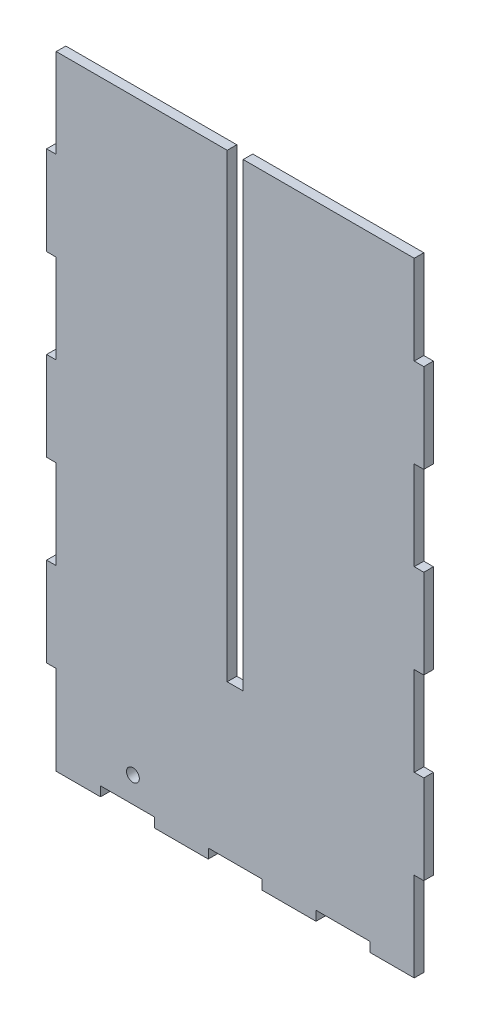
SolidWorks part; units mm, degrees
ref_plane "Front Plane" through (0, 0, 0) normal (0, 0, 1) x (1, 0, 0)
ref_plane "Top Plane" through (0, 0, 0) normal (0, 1, 0) x (1, 0, 0)
ref_plane "Right Plane" through (0, 0, 0) normal (1, 0, 0) x (0, 0, -1)
sketch "Sketch2" plane through (0, 0, 0) normal (0, 0, 1) x (1, 0, 0)
  line L0 (0, 152.4) -> (0, -152.4) construction
  line L1 (-88.9, 152.4) -> (88.9, 152.4)
  line L2 (-88.9, 152.4) -> (-88.9, -152.4)
  line L3 (-88.9, -152.4) -> (88.9, -152.4)
  line L4 (88.9, 152.4) -> (88.9, -152.4)
  line L5 (-88.9, 108.1768) -> (-88.9, 63.9536)
  line L6 (-88.9, 152.4) -> (-93.6625, 152.4)
  line L7 (-88.9, 152.4) -> (-88.9, 108.1768)
  line L8 (-88.9, 108.1768) -> (-93.6625, 108.1768)
  line L9 (-93.6625, 152.4) -> (-93.6625, 108.1768)
  line L10 (88.9, 152.4) -> (93.6625, 152.4)
  line L11 (88.9, 152.4) -> (88.9, 108.1768)
  line L12 (88.9, 108.1768) -> (93.6625, 108.1768)
  line L13 (93.6625, 152.4) -> (93.6625, 108.1768)
  line L14 (-66.9018, -152.4) -> (-93.6625, -152.4)
  line L15 (-66.9018, -152.4) -> (-66.9018, -157.1625)
  line L16 (-66.9018, -157.1625) -> (-93.6625, -157.1625)
  line L17 (-93.6625, -152.4) -> (-93.6625, -157.1625)
  line L18 (-88.9, 108.1768) -> (-93.6625, 108.1768)
  line L19 (-93.6625, 108.1768) -> (-93.6625, 63.9536)
  line L20 (-88.9, 63.9536) -> (-93.6625, 63.9536)
  line L21 (88.9, 108.1768) -> (88.9, 63.9536)
  line L22 (88.9, 108.1768) -> (93.6625, 108.1768)
  line L23 (93.6625, 108.1768) -> (93.6625, 63.9536)
  line L24 (88.9, 63.9536) -> (93.6625, 63.9536)
  line L25 (-88.9, 63.9536) -> (-88.9, 19.7304)
  line L26 (-88.9, 63.9536) -> (-93.6625, 63.9536)
  line L27 (-93.6625, 63.9536) -> (-93.6625, 19.7304)
  line L28 (-88.9, 19.7304) -> (-93.6625, 19.7304)
  line L29 (88.9, 63.9536) -> (88.9, 19.7304)
  line L30 (88.9, 63.9536) -> (93.6625, 63.9536)
  line L31 (93.6625, 63.9536) -> (93.6625, 19.7304)
  line L32 (88.9, 19.7304) -> (93.6625, 19.7304)
  line L33 (-88.9, 19.7304) -> (-88.9, -24.4929)
  line L34 (-88.9, 19.7304) -> (-93.6625, 19.7304)
  line L35 (-93.6625, 19.7304) -> (-93.6625, -24.4929)
  line L36 (-88.9, -24.4929) -> (-93.6625, -24.4929)
  line L37 (88.9, 19.7304) -> (88.9, -24.4929)
  line L38 (88.9, 19.7304) -> (93.6625, 19.7304)
  line L39 (93.6625, 19.7304) -> (93.6625, -24.4929)
  line L40 (88.9, -24.4929) -> (93.6625, -24.4929)
  line L41 (-88.9, -24.4929) -> (-88.9, -68.7161)
  line L42 (-88.9, -24.4929) -> (-93.6625, -24.4929)
  line L43 (-93.6625, -24.4929) -> (-93.6625, -68.7161)
  line L44 (-88.9, -68.7161) -> (-93.6625, -68.7161)
  line L45 (88.9, -24.4929) -> (88.9, -68.7161)
  line L46 (88.9, -24.4929) -> (93.6625, -24.4929)
  line L47 (93.6625, -24.4929) -> (93.6625, -68.7161)
  line L48 (88.9, -68.7161) -> (93.6625, -68.7161)
  line L49 (-88.9, -68.7161) -> (-88.9, -112.9393)
  line L50 (-88.9, -68.7161) -> (-93.6625, -68.7161)
  line L51 (-93.6625, -68.7161) -> (-93.6625, -112.9393)
  line L52 (-88.9, -112.9393) -> (-93.6625, -112.9393)
  line L53 (88.9, -68.7161) -> (88.9, -112.9393)
  line L54 (88.9, -68.7161) -> (93.6625, -68.7161)
  line L55 (93.6625, -68.7161) -> (93.6625, -112.9393)
  line L56 (88.9, -112.9393) -> (93.6625, -112.9393)
  line L57 (-88.9, -112.9393) -> (-88.9, -157.1625)
  line L58 (-88.9, -112.9393) -> (-93.6625, -112.9393)
  line L59 (-93.6625, -112.9393) -> (-93.6625, -157.1625)
  line L60 (-88.9, -157.1625) -> (-93.6625, -157.1625)
  line L61 (88.9, -112.9393) -> (88.9, -157.1625)
  line L62 (88.9, -112.9393) -> (93.6625, -112.9393)
  line L63 (93.6625, -112.9393) -> (93.6625, -157.1625)
  line L64 (88.9, -157.1625) -> (93.6625, -157.1625)
  line L65 (-40.1411, -152.4) -> (-40.1411, -157.1625)
  line L66 (-40.1411, -152.4) -> (-66.9018, -152.4)
  line L67 (-66.9018, -152.4) -> (-66.9018, -157.1625)
  line L68 (-40.1411, -157.1625) -> (-66.9018, -157.1625)
  line L69 (-13.3804, -152.4) -> (-13.3804, -157.1625)
  line L70 (-13.3804, -152.4) -> (-40.1411, -152.4)
  line L71 (-40.1411, -152.4) -> (-40.1411, -157.1625)
  line L72 (-13.3804, -157.1625) -> (-40.1411, -157.1625)
  line L73 (13.3804, -152.4) -> (13.3804, -157.1625)
  line L74 (13.3804, -152.4) -> (-13.3804, -152.4)
  line L75 (-13.3804, -152.4) -> (-13.3804, -157.1625)
  line L76 (13.3804, -157.1625) -> (-13.3804, -157.1625)
  line L77 (40.1411, -152.4) -> (40.1411, -157.1625)
  line L78 (40.1411, -152.4) -> (13.3804, -152.4)
  line L79 (13.3804, -152.4) -> (13.3804, -157.1625)
  line L80 (40.1411, -157.1625) -> (13.3804, -157.1625)
  line L81 (66.9018, -152.4) -> (66.9018, -157.1625)
  line L82 (66.9018, -152.4) -> (40.1411, -152.4)
  line L83 (40.1411, -152.4) -> (40.1411, -157.1625)
  line L84 (66.9018, -157.1625) -> (40.1411, -157.1625)
  line L85 (93.6625, -152.4) -> (93.6625, -157.1625)
  line L86 (93.6625, -152.4) -> (66.9018, -152.4)
  line L87 (66.9018, -152.4) -> (66.9018, -157.1625)
  line L88 (93.6625, -157.1625) -> (66.9018, -157.1625)
  point P6 (0, 0)
  dimension "D1" = 177.8
  dimension "D2" = 187.325
  dimension "D3" = 304.8
  dimension "D4" = 309.5625
  dimension "D6" = 44.2232
  dimension "D8" = 26.7607
  dimension "D5" = 7
  dimension "D7" = 7
extrude "Boss-Extrude1" add sketch "Sketch2" along normal blind 4.7625 contours L0 L1 L2 L3 | L1 L0 L3 L4 | L20 L2 L8 L19 | L36 L2 L28 L35 | L52 L2 L44 L51 | L3 L57 L16 L15 | L72 L69 L3 L65 | L80 L77 L3 L73 | L4 L56 L55 L48 | L4 L40 L39 L32 | L4 L24 L23 L12 | L88 L61 L3 L81 region at (44.45, 0, 0) region at (-44.45, 0, 0) region at (-26.7607, -154.7812, 0) region at (26.7607, -154.7813, 0) region at (-91.2812, 86.0652, 0) region at (91.2813, 86.0652, 0) region at (-77.9009, -154.7813, 0) region at (77.9009, -154.7813, 0) region at (-91.2812, -2.3813, 0) region at (91.2813, -2.3813, 0) region at (-91.2812, -90.8277, 0) region at (91.2813, -90.8277, 0)
sketch "Sketch3" plane through (0, 0, 4.7625) normal (0, 0, 1) x (1, 0, 0)
  line L0 (-88.9, 152.4) -> (88.9, 152.4) construction
  line L1 (-3.9688, 152.4) -> (3.9687, 152.4)
  line L2 (-3.9688, 152.4) -> (-3.9687, -76.2)
  line L3 (-3.9687, -76.2) -> (3.9688, -76.2)
  line L4 (3.9687, 152.4) -> (3.9688, -76.2)
  line L5 (0, -76.2) -> (0, 0) construction
  dimension "D1" = 7.9375
  dimension "D2" = 228.6
extrude "Cut-Extrude1" cut sketch "Sketch3" against normal through all
sketch "Sketch4" plane through (0, 0, 4.7625) normal (0, 0, 1) x (1, 0, 0)
  line L0 (-66.9018, -152.4) -> (-40.1411, -152.4) construction
  line L1 (-88.9, -112.9393) -> (-88.9, -157.1625) construction
  circle A0 centre (-50.8, -139.7) radius 3.175
  dimension "D1" = 6.35
  dimension "D2" = 12.7
  dimension "D3" = 38.1
extrude "Cut-Extrude2" cut sketch "Sketch4" against normal through all
equation "\"Height\"= 12in"
equation "\"Depth\"= 7in"
equation "\"WallThickness\"= 0.1875in"
equation "\"FloorThickness\"= 0.1875in"
equation "\"D1@Sketch2\"=\"Depth\""
equation "\"D2@Sketch2\"=\"D1@Sketch2\"+2*\"WallThickness\""
equation "\"D3@Sketch2\"=\"Height\""
equation "\"D4@Sketch2\"=\"D3@Sketch2\"+\"WallThickness\""
equation "\"D6@Sketch2\"=\"D4@Sketch2\"/\"D5@Sketch2\""
equation "\"D8@Sketch2\"=\"D2@Sketch2\"/\"D7@Sketch2\""
equation "\"D1@Boss-Extrude1\"=\"WallThickness\""
equation "\"Width\" = 30in"
